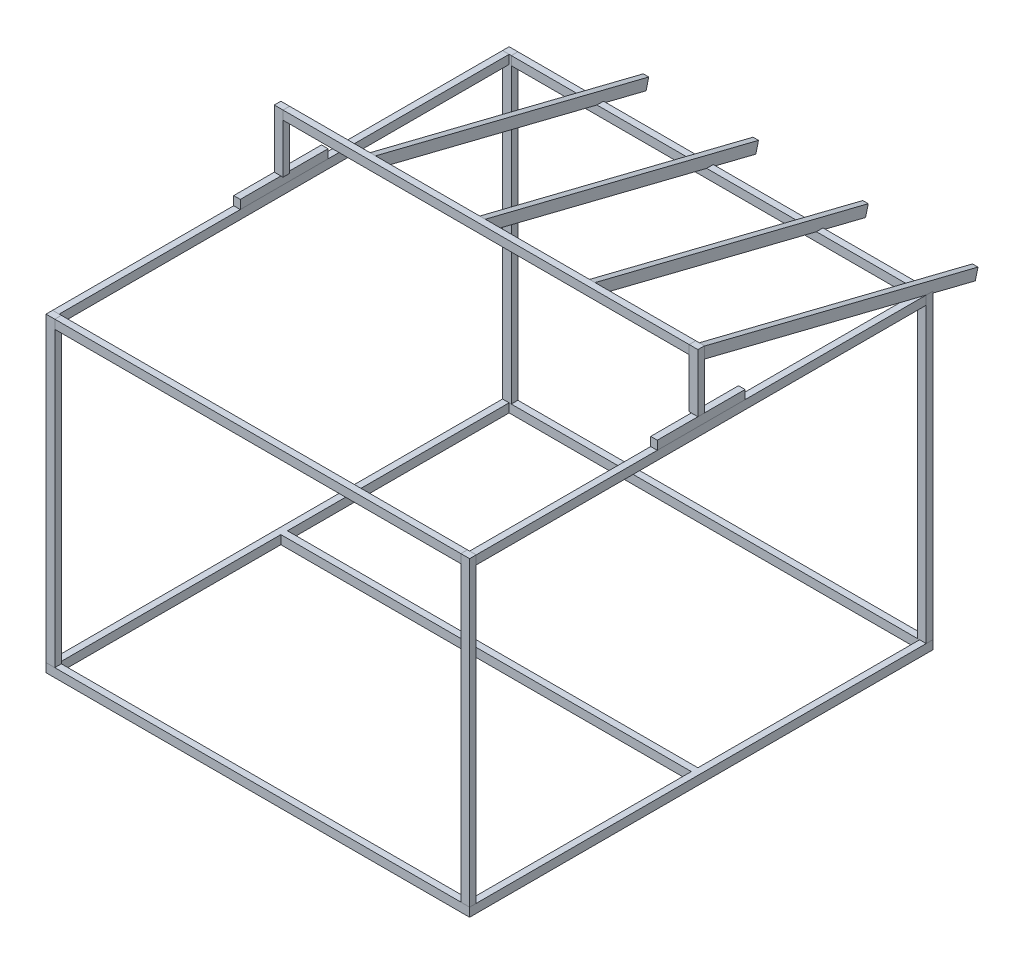
SolidWorks part; units mm, degrees
ref_plane "Front Plane" through (0, 0, 0) normal (0, 0, 1) x (1, 0, 0)
ref_plane "Top Plane" through (0, 0, 0) normal (0, 1, 0) x (1, 0, 0)
ref_plane "Right Plane" through (0, 0, 0) normal (1, 0, 0) x (0, 0, -1)
other "Configuration Table"
sketch "MetalBase" plane through (0, 0, 0) normal (0, 1, 0) x (1, 0, 0)
  line L0 (-60, -60) -> (7660, -60)
  line L1 (0, 0) -> (7600, 0)
  line L2 (0, 0) -> (0, 2020)
  line L3 (0, 4100) -> (7600, 4100)
  line L4 (7600, 0) -> (7600, 2020)
  line L5 (7660, -60) -> (7660, 4160)
  line L6 (-60, 4160) -> (7660, 4160)
  line L7 (-60, -60) -> (-60, 4160)
  line L8 (0, 2050) -> (7600, 2050) construction
  line L9 (0, 2020) -> (7600, 2020)
  line L10 (0, 2080) -> (7600, 2080)
  line L11 (0, 2080) -> (0, 4100)
  line L12 (7600, 2080) -> (7600, 4100)
  line L13 (0, 0) -> (0, 4100) construction
  line L15 (7600, 0) -> (7600, 4100) construction
  point P15 (7660, 2050)
  dimension "D1" = 4100
  dimension "D2" = 7600
  dimension "D6" = 4220
  dimension "D7" = 7720
  dimension "D3" = 60
  dimension "D4" = 30
  dimension "D5" = 30
sketch "InternalSpace" plane through (0, 0, 0) normal (0, 1, 0) x (1, 0, 0)
  line L26 (50, 50) -> (7550, 50)
  line L27 (7550, 50) -> (7550, 4050)
  line L28 (7550, 4050) -> (50, 4050)
  line L29 (50, 4050) -> (50, 50)
  line L30 (50, 50) -> (7550, 50)
  line L31 (7550, 50) -> (7550, 4050)
  line L32 (7550, 4050) -> (50, 4050)
  line L33 (50, 4050) -> (50, 50)
  dimension "D2" = 4000
  dimension "D3" = 7500
  dimension "D1" = 110
sketch "Furniture" plane through (0, 0, 0) normal (0, 1, 0) x (1, 0, 0)
  line L0 (6750, 2050) -> (6750, 4050)
  line L1 (2200, 2550) -> (1400, 2550)
  line L2 (2200, 2550) -> (2200, 4050)
  line L3 (2200, 4050) -> (1400, 4050)
  line L4 (1400, 2550) -> (1400, 4050)
  line L5 (1050, 50) -> (50, 50)
  line L6 (1050, 50) -> (1050, 2050)
  line L7 (1050, 2050) -> (50, 2050)
  line L8 (50, 50) -> (50, 2050)
  line L9 (6350, 2110) -> (7550, 2110)
  line L10 (2200, 4050) -> (2200, 150)
  line L11 (0, 0) -> (7600, 0) construction
  line L12 (6350, 50) -> (6350, 2110)
  line L13 (6470, 50) -> (6470, 1990)
  line L15 (2200, 2050) -> (7550, 2050) construction
  line L17 (1979.5569, 919.0285) -> (2200, 150)
  line L18 (6350, 150) -> (5722.0427, 459.305)
  line L19 (6710, 1120.0467) -> (7310, 1120.0467)
  line L24 (6710, 1120.0467) -> (6710, 1880.0467)
  line L25 (6710, 1880.0467) -> (7310, 1880.0467)
  line L26 (7310, 1120.0467) -> (7310, 1880.0467)
  line L27 (6350, 2110) -> (5750, 2110)
  line L28 (6350, 2110) -> (6350, 1510)
  line L29 (6350, 1510) -> (5750, 1510)
  line L30 (5750, 2110) -> (5750, 1510)
  line L31 (2320, 2050) -> (4320, 2050) construction
  line L32 (4320, 2050) -> (4320, 4050) construction
  line L33 (2200, 150) -> (2499.3532, 150) construction
  line L34 (2499.3532, 150) -> (2499.3532, 981.1813) construction
  line L35 (2499.3532, 981.1813) -> (2200, 981.1813) construction
  line L36 (2320, 4050) -> (2320, 150)
  line L37 (2200, 150) -> (2200, 50)
  line L38 (50, 50) -> (7550, 50) construction
  line L39 (2320, 150) -> (2320, 50)
  line L40 (7550, 4050) -> (50, 4050) construction
  line L41 (7550, 50) -> (7550, 4050) construction
  line L42 (50, 4050) -> (50, 50) construction
  line L43 (7550, 4050) -> (50, 4050) construction
  line L44 (7550, 50) -> (7550, 4050) construction
  line L45 (50, 50) -> (7550, 50) construction
  line L46 (50, 4050) -> (50, 50) construction
  line L47 (7010, 1120.0467) -> (7010, 1445.9123) construction
  line L48 (6470, 1990) -> (7550, 1990)
  line L49 (-60, -60) -> (-60, 4160) construction
  line L50 (7550, 809.8905) -> (7383.7397, 809.8905)
  line L51 (7550, 809.8905) -> (7550, 230.8186)
  line L52 (7550, 230.8186) -> (7383.7397, 230.8186)
  line L53 (7283.7397, 709.8905) -> (7283.7397, 330.8186)
  line L54 (7660, 4160) -> (-60, 4160) construction
  line L55 (-60, 4160) -> (-60, -60) construction
  line L56 (-60, -60) -> (7660, -60) construction
  line L57 (7660, -60) -> (7660, 4160) construction
  arc A1 (1979.5569, 919.0285) -> (1414.1883, 0) centre (2200, 150) ccw construction
  arc A2 (5722.0427, 459.305) -> (6350, 850) centre (6350, 150) cw construction
  arc A3 (7383.7397, 230.8186) -> (7283.7397, 330.8186) centre (7383.7397, 330.8186) cw
  arc A4 (7383.7397, 809.8905) -> (7283.7397, 709.8905) centre (7383.7397, 709.8905) ccw
  point P56 (7010, 1990)
  dimension "D13" = 600
  dimension "D21" = 100
  dimension "D1" = 1500
  dimension "D2" = 800
  dimension "D3" = 2000
  dimension "D4" = 1000
  dimension "D5" = 100
  dimension "D6" = 60
  dimension "D7" = 700
  dimension "D8" = 600
  dimension "D9" = 2260
  dimension "D10" = 800
  dimension "D11" = 100
  dimension "D12" = 760
  dimension "D14" = 2000
  dimension "D15" = 800
  dimension "D16" = 2000
  dimension "D17" = 600
  dimension "D18" = 60
  dimension "D19" = 4150
  dimension "D20" = 120
  dimension "D22" = 120
  dimension "D23" = 110
  dimension "D25" = 4220
  dimension "D26" = 1200
  dimension "D27" = 4030
  dimension "D24" = 110
sketch "Metal frame" plane through (0, 0, 0) normal (0, 1, 0) x (1, 0, 0)
  line L0 (0, 4100) -> (7600, 4100) construction
  line L1 (0, 4100) -> (7600, 4100)
  line L3 (0, 0) -> (0, 2020)
  line L4 (0, 0) -> (7600, 0) construction
  line L5 (0, 0) -> (7600, 0)
  line L7 (7600, 0) -> (7600, 2020)
  line L8 (-60, 4160) -> (7660, 4160)
  line L9 (7660, -60) -> (7660, 4160)
  line L10 (-60, -60) -> (7660, -60)
  line L11 (-60, -60) -> (-60, 4160)
  line L12 (0, 2050) -> (62.1159, 2050) construction
  line L13 (7600, 2080) -> (0, 2080)
  line L15 (7600, 2020) -> (0, 2020)
  line L17 (7600, 2080) -> (7600, 4100)
  line L18 (0, 2080) -> (0, 4100)
  line L19 (7600, 0) -> (7600, 4100) construction
  line L21 (0, 0) -> (0, 4100) construction
  point P14 (-60, 2050)
  dimension "D2" = 7720
  dimension "D3" = 4220
  dimension "D4" = 60
  dimension "D1" = 60
sketch "Walls bottom" plane through (0, 0, 0) normal (0, 1, 0) x (1, 0, 0)
  line L0 (-60, 4160) -> (7660, 4160) construction
  line L2 (-60, -60) -> (7660, -60) construction
  line L3 (7660, -60) -> (7660, 4160) construction
  line L4 (-60, -60) -> (-60, 4160) construction
  line L5 (-60, -60) -> (7660, -60)
  line L6 (7660, -60) -> (7660, 4160)
  line L7 (-60, 4160) -> (7660, 4160)
  line L8 (-60, -60) -> (-60, 4160)
  line L9 (40, 40) -> (40, 4060)
  line L10 (40, 4060) -> (7560, 4060)
  line L11 (7560, 40) -> (7560, 4060)
  line L12 (40, 40) -> (7560, 40)
  dimension "D2" = 4020
  dimension "D3" = 7520
  dimension "D4" = 7720
  dimension "D5" = 4220
  dimension "D1" = 100
sketch "Sketch15" plane through (0, 0, 0) normal (0, 1, 0) x (1, 0, 0)
  line L2 (7550, 50) -> (5502.4266, 50)
  line L3 (7550, 50) -> (7550, 1250)
  line L4 (7550, 1250) -> (5502.4266, 1250)
  line L5 (5502.4266, 50) -> (5502.4266, 1250)
  dimension "D1" = 1200
extrude "MetalFrame" add sketch "Metal frame" against normal blind 80 contours L11 L10 L9 L8 L15 L7 L5 L3 L13 L18 L1 L17 region at (3800, 0, -2050)
sketch "Sketch18" plane through (0, 0, 0) normal (0, 1, 0) x (1, 0, 0)
  line L0 (0, 0) -> (7600, 0) construction
  line L1 (3800, -1014.8769) -> (8467.9433, -1014.8769)
  line L2 (3800, -1014.8769) -> (3800, 5493.3133)
  line L3 (3800, 5493.3133) -> (8467.9433, 5493.3133)
  line L4 (8467.9433, -1014.8769) -> (8467.9433, 5493.3133)
  point P6 (3800, 0)
extrude "Cut-Extrude1" cut sketch "Sketch18" against normal through all
sketch "Sketch19" plane through (0, 0, 0) normal (0, 1, 0) x (1, 0, 0)
  line L0 (0, 0) -> (3800, 0) construction
  line L1 (3800, 4100) -> (3740, 4100)
  line L2 (3800, 4100) -> (3800, 0)
  line L3 (3800, 0) -> (3740, 0)
  line L4 (3740, 4100) -> (3740, 0)
  dimension "D1" = 60
extrude "Boss-Extrude1" add sketch "Sketch19" against normal blind 80
sketch "Roof" plane through (0, 0, 0) normal (1, 0, 0) x (0, 0, -1)
  line L0 (2050, 0) -> (2050, 3277.5) construction
  line L1 (4160, 0) -> (-60, 0) construction
  line L2 (4160, 0) -> (4160, 2750) construction
  line L3 (4160, 2750) -> (2050, 3277.5) construction
  line L4 (2050, 3277.5) -> (5424.8088, 3277.5) construction
  line L5 (4160, 2750) -> (4548.057, 2652.9857) construction
  line L6 (4160, 150) -> (-211.81, 150) construction
  line L7 (4160, 2750) -> (2960, 2750)
  line L8 (2960, 2750) -> (2960, 3050)
  dimension "D1" = 2600
  dimension "D2" = 1200
  dimension "D3" = 150
  dimension "D4" = 2174.9382
  dimension "D5" = 400
  dimension "D6" = 2574.9382
  dimension "D7" = 2750
  dimension "D8" = 300
  dimension "D9" = 3127.5
  dimension "D10" = 14.036
sketch "Sketch23" plane through (-60, 0, 0) normal (1, 0, 0) x (0, 0, -1)
  line L0 (2050, 0) -> (2050, 3277.5) construction
  line L1 (4160, 0) -> (4100, 0)
  line L2 (4160, 0) -> (4160, 2750)
  line L3 (4160, 2750) -> (4100, 2750)
  line L4 (4100, 0) -> (4100, 2750)
  line L5 (0, 0) -> (0, 2750)
  line L6 (-60, 2750) -> (0, 2750)
  line L7 (-60, 0) -> (-60, 2750)
  line L8 (-60, 0) -> (0, 0)
  line L10 (0, 2750) -> (4100, 2750)
  line L11 (0, 2750) -> (0, 2670)
  line L12 (0, 2670) -> (4100, 2670)
  line L13 (4100, 2750) -> (4100, 2670)
  line M8 (-60, 0) -> (4160, 0)
  dimension "D1" = 60
  dimension "D2" = 80
extrude "Boss-Extrude5" add sketch "Sketch23" along normal blind 80 separate body contours L4 L3 L2 M8 | L7 L6 L5 M8 region at (-60, 1375, -4130) region at (-60, 1375, 30)
extrude "Boss-Extrude6" add sketch "Sketch23<3>" along normal blind 60 separate body contours L0 L12 L5 L10 | L12 L0 L10 L4 region at (-60, 2710, -1025) region at (-60, 2710, -3075)
sketch "Sketch23<3>" plane through (-60, 0, 0) normal (1, 0, 0) x (0, 0, -1) same geometry as "Sketch23"
extrude "Boss-Extrude7" add sketch "Sketch23<5>" against normal blind 80 from surface separate body contours L4 L3 L2 M8 | L7 L6 L5 M8 region at (-60, 1375, -4130) region at (-60, 1375, 30) starting at face at (3800, -40, -2050)
sketch "Sketch23<5>" plane through (-60, 0, 0) normal (1, 0, 0) x (0, 0, -1) same geometry as "Sketch23"
extrude "Boss-Extrude8" add sketch "Sketch23<6>" against normal blind 60 from surface separate body contours L12 L0 L10 L4 | L0 L12 L5 L10 region at (-60, 2710, -1025) region at (-60, 2710, -3075) starting at face at (3800, 1375, 30)
sketch "Sketch23<6>" plane through (-60, 0, 0) normal (1, 0, 0) x (0, 0, -1) same geometry as "Sketch23"
sketch "Sketch24" plane through (0, 2750, 0) normal (0, 1, 0) x (1, 0, 0)
  line L1 (20, 4160) -> (3720, 4160)
  line L2 (20, 4160) -> (20, 4100)
  line L3 (20, 4100) -> (3720, 4100)
  line L4 (3720, 4160) -> (3720, 4100)
  line L5 (20, 0) -> (3720, 0)
  line L6 (20, 0) -> (20, -60)
  line L7 (20, -60) -> (3720, -60)
  line L8 (3720, 0) -> (3720, -60)
extrude "Boss-Extrude9" add sketch "Sketch24" against normal blind 80 separate body
sketch "Sketch25" plane through (3800, 0, 0) normal (1, 0, 0) x (0, 0, -1)
  line L5 (2020, 2830) -> (2080, 2830)
  line L6 (2020, 2830) -> (2020, 3360)
  line L7 (2020, 3360) -> (2080, 3360)
  line L8 (2080, 2830) -> (2080, 3360)
  line L9 (2050, 0) -> (2050, 3277.5) construction
  line L10 (0, 2750) -> (4100, 2750) construction
  line L12 (1650, 2750) -> (2450, 2750)
  line L13 (1650, 2750) -> (1650, 2830)
  line L14 (1650, 2830) -> (2450, 2830)
  line L15 (2450, 2750) -> (2450, 2830)
  point P7 (2050, 3360)
  point P11 (2050, 2830)
  line M8 (4100, 2750) -> (0, 2750)
  dimension "D1" = 530
  dimension "D2" = 60
  dimension "D4" = 800
  dimension "D5" = 80
extrude "Boss-Extrude10" add sketch "Sketch25" against normal blind 80 separate body contours L5 L8 L7 L6 region at (3800, 3095, -2050)
extrude "Boss-Extrude13" add sketch "Sketch25<4>" against normal blind 60 separate body contours L15 L14 L5 L13 M8 region at (3800, 2790, -2050)
sketch "Sketch25<4>" plane through (3800, 0, 0) normal (1, 0, 0) x (0, 0, -1) same geometry as "Sketch25"
sketch "Sketch26" plane through (3800, 0, 0) normal (1, 0, 0) x (0, 0, -1)
  line L0 (4548.057, 2637.9857) -> (4160, 2735)
  line L1 (4548.057, 2637.9857) -> (4572.3106, 2735)
  line L3 (4572.3106, 2735) -> (2080, 3358.0776)
  line L4 (4100, 2735) -> (4100, 2750) construction
  line L5 (4100, 2750) -> (4160, 2750)
  line L6 (4160, 2750) -> (4160, 2735)
  line L7 (2080, 3255) -> (2080, 3358.0776)
  line L8 (4100, 2750) -> (2080, 3255)
  dimension "D1" = 100
extrude "Boss-Extrude12" add sketch "Sketch26" against normal blind 50 separate body
pattern_linear "LPattern1" count 4 spacing 1000 along (-1, 0, 0) of bodies 346
ref_plane "Plane1" through (1870, 0, 0) normal (-1, 0, 0) x (0, 0, 1)
mirror "Mirror1" about plane through (1870, 0, 0) normal (-1, 0, 0) of bodies 351 350
sketch "Sketch27" plane through (3720, 0, 0) normal (-1, 0, 0) x (0, 0, 1)
  line L0 (-2020, 2830) -> (-2020, 3360) construction
  line L1 (-2080, 3360) -> (-2020, 3360)
  line L2 (-2080, 3360) -> (-2080, 3280)
  line L3 (-2080, 3280) -> (-2020, 3280)
  line L4 (-2020, 3360) -> (-2020, 3280)
  point P7 (0, 0)
  dimension "D1" = 80
  dimension "D2" = 60
extrude "Boss-Extrude14" add sketch "Sketch27" along normal up to surface (3700 mm away) separate body up to face at (20, 3095, -2050)
